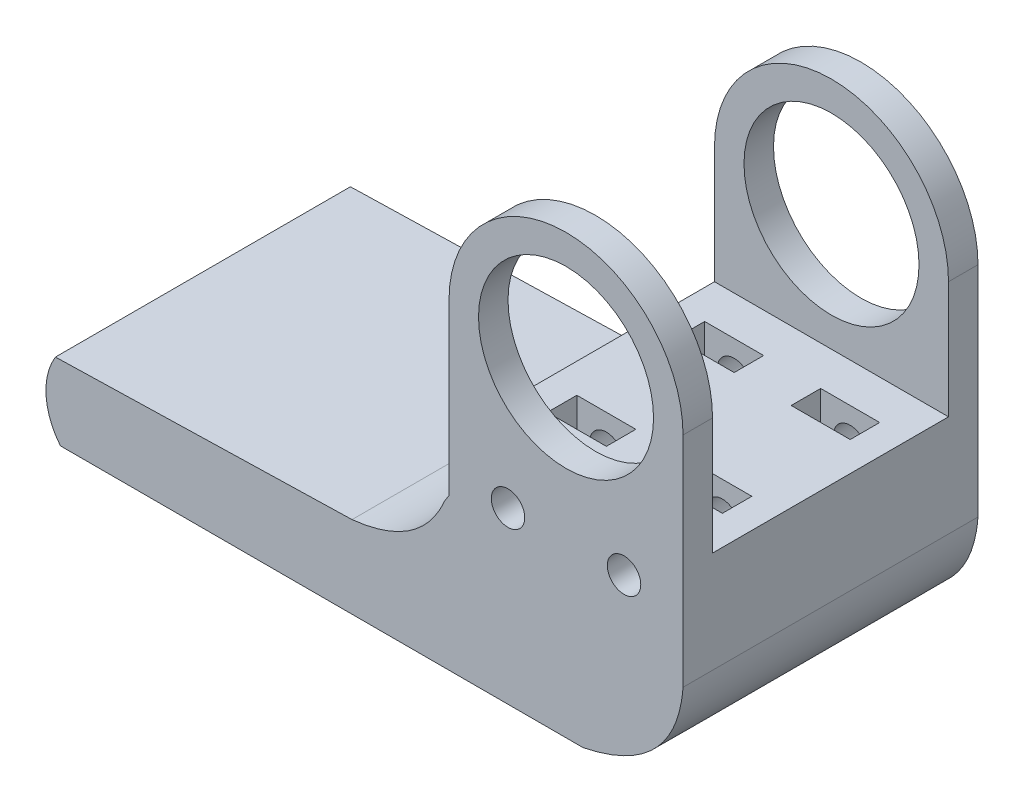
SolidWorks part; units mm, degrees
ref_plane "Front Plane" through (0, 0, 0) normal (0, 0, 1) x (1, 0, 0)
ref_plane "Top Plane" through (0, 0, 0) normal (0, 1, 0) x (1, 0, 0)
ref_plane "Right Plane" through (0, 0, 0) normal (1, 0, 0) x (0, 0, -1)
sketch "Sketch1" plane through (0, 0, 0) normal (0, 0, 1) x (1, 0, 0)
  line L0 (-11.9, 0) -> (-11.9, -17.2546)
  line L1 (-11.9, -17.2546) -> (-12.3014, -17.8366)
  line L4 (-51.4207, -32.6222) -> (1.7322, -32.6222)
  line L6 (11.9, -22.2213) -> (11.9, 0)
  line L7 (-21.7646, -24.2845) -> (-51.9306, -25.0496)
  circle A0 centre (0, 0) radius 8.9
  arc A1 (11.9, 0) -> (-11.9, 0) centre (0, 0) ccw
  arc A2 (-51.9306, -25.0496) -> (-51.4207, -32.6222) centre (-46.3598, -28.478) ccw
  spline S0 degree 2 poles (1.7322, -32.6222) (11.2482, -30.6652) (11.9, -22.2213) knots 0 0 0 1 1 1
  spline S1 degree 2 poles (-21.7646, -24.2845) (-14.0586, -23.4565) (-11.9, -16.7527) knots 0 0 0 1 1 1
  dimension "D1" = 17.8
  dimension "D2" = 23.8
  dimension "D3" = 53.1529
  dimension "D4" = 30.1757
extrude "Boss-Extrude1" add sketch "Sketch1" along normal blind 30 contours S1 L7 A2 L4 S0 L6 A1 L0 L1 A0 region at (-10.2152, -19.1798, 0)
sketch "Sketch2" plane through (-11.9, 0, 0) normal (-1, 0, 0) x (0, 0, 1)
  line L0 (0, 0) -> (0, -17.2546) construction
  line L1 (3, -11.9) -> (27, -11.9)
  line L2 (3, -11.9) -> (3, 11.9)
  line L3 (3, 11.9) -> (27, 11.9)
  line L4 (27, -11.9) -> (27, 11.9)
  line L5 (30, 0) -> (30, -17.2546) construction
  line L6 (30, 11.9) -> (0, 11.9) construction
  dimension "D1" = 3
  dimension "D2" = 3
  dimension "D3" = 23.8
extrude "Cut-Extrude1" cut sketch "Sketch2" against normal up to surface (23.8 mm away) up to face at (11.9, -11.1106, 15)
hole_wizard "M3 Clearance Hole1" positions "3DSketch1" profile "Sketch3" hole size "M3" standard "ANSI Metric" end condition through all
sketch3d "3DSketch1"
  circle A0 centre (-5.9, -15.34, 30) radius 1.7 construction
  circle A1 centre (5.9, -15.34, 30) radius 1.7 construction
  point P0 (-5.9, -15.34, 30)
  point P2 (5.9, -15.34, 30)
  point P5 (0, 0, 0)
  point P8 (-5.9, -15.34, 31.7)
  point P11 (5.9, -15.34, 31.7)
  point P12 (0, 0, 0)
sketch "Sketch3" plane through (-5.9, -15.34, 30) normal (1, 0, 0) x (0, -1, 0)
  line L0 (0, 0) -> (0, 30)
  line L1 (0, 30) -> (1.7, 30)
  line L2 (1.7, 30) -> (1.7, 0)
  line L5 (1.7, 0) -> (0, 0)
  line L11 (0, -6.35) -> (0, 107.95) construction
  dimension "Thru Hole Dia." = 3.4
  dimension "Thru Hole Depth" = 30
sketch "Sketch4" plane through (0, -11.9, 0) normal (0, 1, 0) x (1, 0, 0)
  line L0 (11.9, -3) -> (-11.9, -3) construction
  line L1 (-8.9, -7) -> (-2.9, -7)
  line L2 (-8.9, -7) -> (-8.9, -10)
  line L3 (-8.9, -10) -> (-2.9, -10)
  line L4 (-2.9, -7) -> (-2.9, -10)
  line L6 (-4.2, 0) -> (-7.6, 0) construction
  line L7 (-4.2, 0) -> (-7.6, 0) construction
  line L8 (0, -3) -> (0, -27) construction
  line L9 (11.9, -27) -> (-11.9, -27) construction
  line L10 (-11.9, -15) -> (11.9, -15) construction
  line L11 (-11.9, -3) -> (-11.9, -27) construction
  line L12 (11.9, -27) -> (11.9, -3) construction
  line L13 (8.9, -10) -> (2.9, -10)
  line L14 (2.9, -7) -> (2.9, -10)
  line L15 (8.9, -7) -> (2.9, -7)
  line L16 (8.9, -7) -> (8.9, -10)
  line L17 (8.9, -23) -> (8.9, -20)
  line L18 (8.9, -23) -> (2.9, -23)
  line L19 (2.9, -23) -> (2.9, -20)
  line L20 (8.9, -20) -> (2.9, -20)
  line L21 (-8.9, -20) -> (-2.9, -20)
  line L22 (-2.9, -23) -> (-2.9, -20)
  line L23 (-8.9, -23) -> (-2.9, -23)
  line L24 (-8.9, -23) -> (-8.9, -20)
  point P7 (-5.9, 0)
  point P8 (-5.9, -7)
  dimension "D1" = 6
  dimension "D2" = 3
  dimension "D3" = 4
extrude "Cut-Extrude2" cut sketch "Sketch4" against normal blind 6.19
